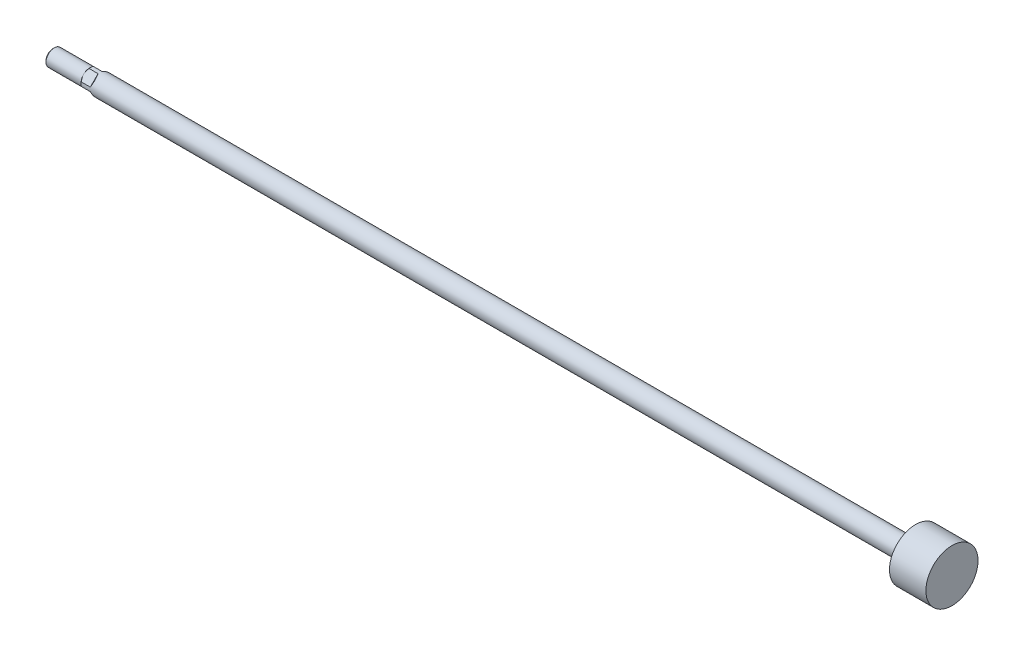
SolidWorks part; units mm, degrees
ref_plane "前视基准面" through (0, 0, 0) normal (0, 0, 1) x (1, 0, 0)
ref_plane "上视基准面" through (0, 0, 0) normal (0, 1, 0) x (1, 0, 0)
ref_plane "右视基准面" through (0, 0, 0) normal (1, 0, 0) x (0, 0, -1)
sketch "草图1" plane through (0, 0, 0) normal (0, 0, 1) x (1, 0, 0)
  line L0 (0, 0) -> (0, 4.233)
  line L1 (0, 4.233) -> (0.767, 5)
  line L2 (0.767, 5) -> (22, 5)
  line L3 (22, 5) -> (23, 6)
  line L4 (23, 6) -> (521, 6)
  line L5 (521, 6) -> (521, 15.75)
  line L6 (521, 15.75) -> (543, 15.75)
  line L7 (543, 15.75) -> (543, 0)
  line L8 (543, 0) -> (0, 0)
  line L9 (543, 0) -> (0, 0) construction
revolve "旋转1" add sketch "草图1" angle 360 about L9 reverse direction yes
cosmetic thread "装饰螺纹线1" parameters "D1"=22, "D2"=8.466
ref_plane "基准面4" through (30, 0, 0) normal (1, 0, 0) x (0, 0, -1)
ref_plane "基准面5" through (11, 0, 0) normal (1, 0, 0) x (0, 0, -1)
ref_plane "基准面6" through (0, 0, 0) normal (0, -0.7071, 0.7071) x (1, 0, 0)
sketch "草图2" plane through (0, 0, 0) normal (0, -0.7071, 0.7071) x (1, 0, 0)
  line L0 (-5, -12) -> (35.4, -12)
  line L1 (35.4, -12) -> (28.4, -5)
  line L2 (28.4, -5) -> (22, -5)
  line L3 (22, -5) -> (19.8, -7.2)
  line L4 (19.8, -7.2) -> (19.8, -10)
  line L5 (19.8, -10) -> (-3, -10)
  line L6 (-3, -10) -> (-3, 10)
  line L7 (-3, 10) -> (19.8, 10)
  line L8 (19.8, 10) -> (19.8, 7.2)
  line L9 (19.8, 7.2) -> (22, 5)
  line L10 (22, 5) -> (28.4, 5)
  line L11 (28.4, 5) -> (35.4, 12)
  line L12 (35.4, 12) -> (-5, 12)
  line L13 (-5, 12) -> (-5, -12)
extrude "切除-拉伸1" cut sketch "草图2" along normal blind 5 and the other way blind 5
ref_plane "基准面7" through (0, 0, 0) normal (0, -0.7071, -0.7071) x (-1, 0, 0)
sketch "草图3" plane through (0, 0, 0) normal (0, -0.7071, -0.7071) x (-1, 0, 0)
  line L0 (5, 12) -> (-35.4, 12)
  line L1 (-35.4, 12) -> (-28.4, 5)
  line L2 (-28.4, 5) -> (-22, 5)
  line L3 (-22, 5) -> (-19.8, 7.2)
  line L4 (-19.8, 7.2) -> (-19.8, 10)
  line L5 (-19.8, 10) -> (3, 10)
  line L6 (3, 10) -> (3, -10)
  line L7 (3, -10) -> (-19.8, -10)
  line L8 (-19.8, -10) -> (-19.8, -7.2)
  line L9 (-19.8, -7.2) -> (-22, -5)
  line L10 (-22, -5) -> (-28.4, -5)
  line L11 (-28.4, -5) -> (-35.4, -12)
  line L12 (-35.4, -12) -> (5, -12)
  line L13 (5, -12) -> (5, 12)
extrude "切除-拉伸2" cut sketch "草图3" along normal blind 5 and the other way blind 5
ref_plane "nut-rod XY" through (11, 0, 0) normal (-1, 0, 0) x (0, 0, 1)
ref_plane "nut-rod XZ" through (0, 0, 0) normal (0, 1, 0) x (1, 0, 0)
ref_plane "nut-rod YZ" through (0, 0, 0) normal (0, 0, -1) x (-1, 0, 0)
ref_axis "nut-rod X" through (11, 0, 80.9) along (0, 0, -1)
ref_axis "nut-rod Y" through (11, 50, 0) along (0, -1, 0)
ref_axis "nut-rod Z" through (-80.9, 0, 0) along (1, 0, 0)
sketch3d "nut-rod"
  point P0 (11, 0, 0)
ref_plane "rod XY" through (30, 0, 0) normal (-1, 0, 0) x (0, 0, 1)
ref_plane "rod XZ" through (0, 0, 0) normal (0, 1, 0) x (1, 0, 0)
ref_plane "rod YZ" through (0, 0, 0) normal (0, 0, -1) x (-1, 0, 0)
ref_axis "rod X" through (30, 0, 80.9) along (0, 0, -1)
ref_axis "rod Y" through (30, 50, 0) along (0, -1, 0)
ref_axis "rod Z" through (-80.9, 0, 0) along (1, 0, 0)
sketch3d "rod"
  point P0 (30, 0, 0)
